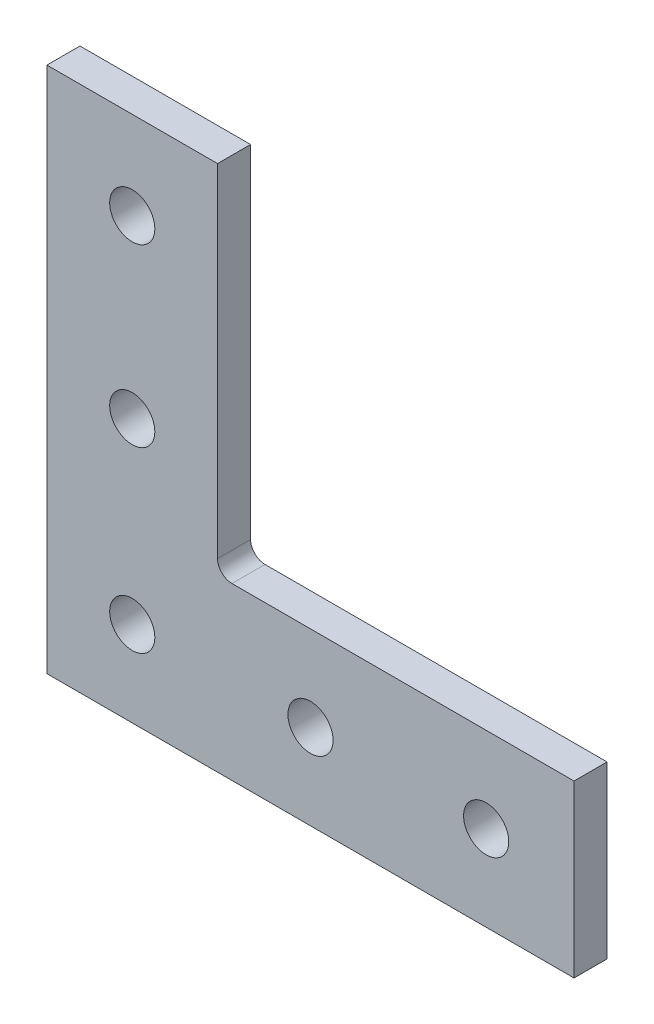
SolidWorks part; units mm, degrees
ref_plane "Front Plane" through (0, 0, 0) normal (0, 0, 1) x (1, 0, 0)
ref_plane "Top Plane" through (0, 0, 0) normal (0, 1, 0) x (1, 0, 0)
ref_plane "Right Plane" through (0, 0, 0) normal (1, 0, 0) x (0, 0, -1)
sketch "Sketch1" plane through (0, 0, 0) normal (0, 0, 1) x (1, 0, 0)
  line L0 (-38.1, -38.1) -> (-38.1, 38.1) construction
  line L1 (38.1, -38.1) -> (-38.1, -38.1) construction
  line L2 (-38.1, 38.1) -> (-13.4366, 38.1) construction
  line L3 (-29.0322, 25.4) -> (-22.5044, 25.4) construction
  point P0 (-25.7683, 38.1)
  point P3 (-25.7683, 0)
  point P4 (-38.1, 0)
  point P6 (-38.1, 38.1)
  point P8 (-38.1, 0)
  point P10 (0, 0)
  point P12 (0, -38.1)
  point P14 (-25.7683, 25.4)
  dimension "Length" = 76.2
  dimension "Width" = 24.6634
  dimension "Hole to Edge" = 12.7
  dimension "Hole Spacing" = 25.4
  dimension "Hole Dia" = 6.5278
sketch "Sketch2" plane through (0, 0, 0) normal (1, 0, 0) x (0, 0, -1)
  line L0 (2.3876, 0) -> (-2.3876, 0) construction
  point P4 (0, 0)
  dimension "Thickness" = 4.7752
sketch "Sketch3" plane through (0, 0, 0) normal (0, 0, 1) x (1, 0, 0)
  line L0 (-13.4366, 38.1) -> (-38.1, 38.1)
  line L1 (-38.1, 38.1) -> (-38.1, -38.1)
  line L2 (-38.1, -38.1) -> (38.1, -38.1)
  line L3 (38.1, -38.1) -> (38.1, -13.4366)
  line L4 (38.1, -13.4366) -> (-11.3538, -13.4366)
  line L5 (-13.4366, -11.3538) -> (-13.4366, 38.1)
  arc A0 (-11.3538, -13.4366) -> (-13.4366, -11.3538) centre (-11.3538, -11.3538) cw
  dimension "Radius" = 2.0828
extrude "Boss-Extrude1" add sketch "Sketch3" against normal up to vertex (2.3876 mm away) and the other way up to vertex (2.3876 mm away) up to point (0, 0, -2.3876) other way up to point (0, 0, 2.3876)
sketch "Sketch4" plane through (0, 0, 2.3876) normal (0, 0, 1) x (1, 0, 0)
  line L0 (-29.0322, 25.4) -> (-22.5044, 25.4) construction
  line L1 (-38.1, -38.1) -> (0, 0) construction
  circle A0 centre (-25.7683, 25.4) radius 3.2639
  circle A1 centre (-25.7683, 0) radius 3.2639
  circle A3 centre (0, -25.7683) radius 3.2639
  circle A4 centre (25.4, -25.7683) radius 3.2639
  circle A5 centre (-25.7683, -25.7683) radius 3.2639
extrude "Cut-Extrude1" cut sketch "Sketch4" against normal through all both and the other way through all
